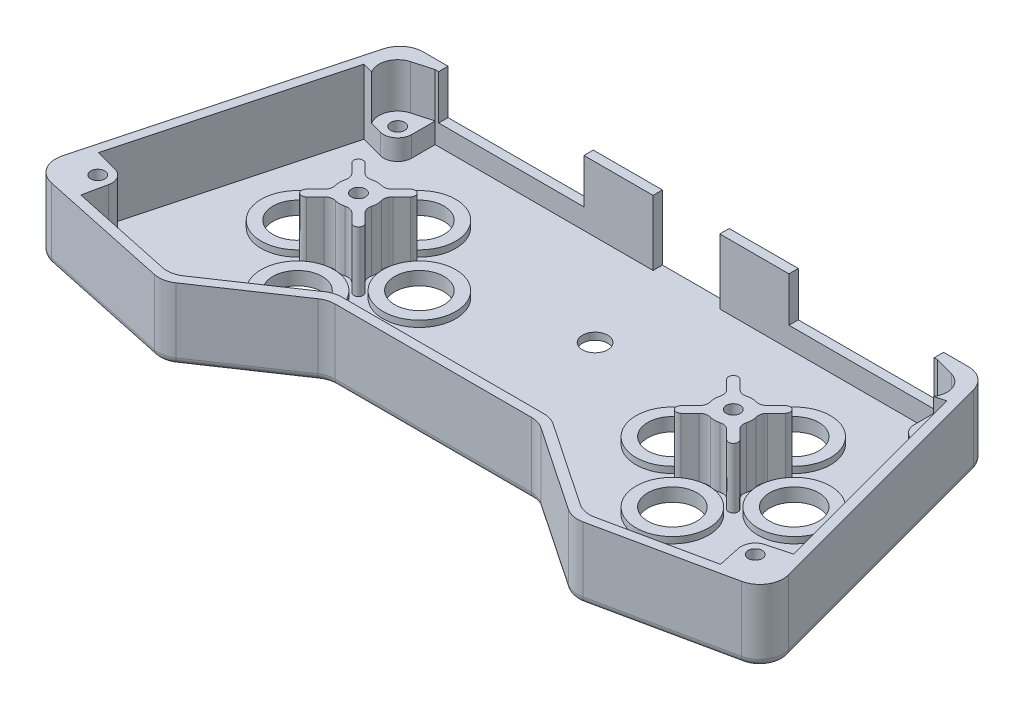
SolidWorks part; units mm, degrees
ref_plane "Front Plane" through (0, 0, 0) normal (0, 0, 1) x (1, 0, 0)
ref_plane "Top Plane" through (0, 0, 0) normal (0, 1, 0) x (1, 0, 0)
ref_plane "Right Plane" through (0, 0, 0) normal (1, 0, 0) x (0, 0, -1)
sketch "Sketch10" plane through (0, 0, 0) normal (0, 1, 0) x (1, 0, 0)
  line L0 (62, 32) -> (-62, 32)
  line L1 (-62, 32) -> (-78.8232, -30.7852)
  line L2 (-78.8232, -30.7852) -> (-43.6451, -38.2625)
  line L3 (-43.6451, -38.2625) -> (-22.5, -24)
  line L4 (-22.5, -24) -> (22.5, -24)
  line L5 (22.5, -24) -> (43.6451, -38.2625)
  line L6 (43.6451, -38.2625) -> (78.8232, -30.7852)
  line L7 (78.8232, -30.7852) -> (62, 32)
  line L8 (40, 13) -> (40, -13) construction
  line L9 (27, 0) -> (53, 0) construction
  line L10 (-40, 13) -> (-40, -13) construction
  line L11 (-53, 0) -> (-27, 0) construction
  line L12 (-27, 0) -> (27, 0) construction
  line L13 (0, 0) -> (0, 32) construction
  line L14 (0, 0) -> (0, -24) construction
  line L15 (78.8232, -30.7852) -> (22.5, -24) construction
  line L16 (-22.5, -24) -> (-78.8232, -30.7852) construction
  circle A0 centre (40, 13) radius 5.25
  circle A1 centre (27, 0) radius 5.25
  circle A2 centre (40, -13) radius 5.25
  circle A3 centre (53, 0) radius 5.25
  circle A4 centre (-40, 13) radius 5.25
  circle A5 centre (-53, 0) radius 5.25
  circle A6 centre (-40, -13) radius 5.25
  circle A7 centre (-27, 0) radius 5.25
  point P16 (40, 0)
  point P17 (-40, 0)
  dimension "D1" = 10.5
  dimension "D2" = 26
  dimension "D3" = 65
  dimension "D4" = 124
  dimension "D5" = 80
  dimension "D6" = 105
  dimension "D7" = 56
  dimension "D8" = 45
  dimension "D9" = 32
  dimension "D10" = 12
  dimension "D11" = 34
extrude "Boss-Extrude5" add sketch "Sketch10" along normal blind 1.5 separate body
sketch "Sketch11" plane through (0, 1.5, 0) normal (0, 1, 0) x (1, 0, 0)
  line L0 (-78.8232, -30.7852) -> (-62, 32)
  line L1 (-62, 32) -> (62, 32)
  line L2 (62, 32) -> (78.8232, -30.7852)
  line L3 (78.8232, -30.7852) -> (43.6451, -38.2625)
  line L4 (43.6451, -38.2625) -> (22.5, -24)
  line L5 (22.5, -24) -> (-22.5, -24)
  line L6 (-22.5, -24) -> (-43.6451, -38.2625)
  line L7 (-43.6451, -38.2625) -> (-78.8232, -30.7852)
  line L8 (-44.0596, -36.1297) -> (-76.3459, -29.2671)
  line L9 (-76.3459, -29.2671) -> (-60.4653, 30)
  line L10 (-60.4653, 30) -> (60.4653, 30)
  line L11 (60.4653, 30) -> (76.3459, -29.2671)
  line L12 (76.3459, -29.2671) -> (44.0596, -36.1297)
  line L13 (44.0596, -36.1297) -> (23.1115, -22)
  line L14 (23.1115, -22) -> (-23.1115, -22)
  line L15 (-23.1115, -22) -> (-44.0596, -36.1297)
  dimension "D1" = 2
extrude "Boss-Extrude7" add sketch "Sketch11" along direction (0, -1, 0) on the side of the normal offset from surface (13.875 mm away) 15.375 up to face at (-40, 0, 18.25)
fillet "Fillet4" radius 5 16 edges at (62, 7.6875, -32) (78.8232, 7.6875, 30.7852) (43.6451, 7.6875, 38.2625) (22.5, 7.6875, 24) (-22.5, 7.6875, 24) (-43.6451, 7.6875, 38.2625) (-62, 7.6875, -32) (-78.8232, 7.6875, 30.7852) (76.3459, 8.4375, 29.2671) (60.4653, 8.4375, -30) (44.0596, 8.4375, 36.1297) (23.1115, 8.4375, 22) (-23.1115, 8.4375, 22) (-44.0596, 8.4375, 36.1297) (-76.3459, 8.4375, 29.2671) (-60.4653, 8.4375, -30)
fillet "Fillet5" radius 1.5 16 edges at (43.7275, 0, 37.8387) (32.8264, 0, 30.9653) (22.4332, 0, 24.2185) (0, 0, 24) (-22.4332, 0, 24.2185) (-32.8264, 0, 30.9653) (-43.7275, 0, 37.8387) (-59.6953, 0, 34.851) (-76.8931, 0, 29.6024) (-70.2263, 0, -1.2991) (-61.2072, 0, -30.9668) (0, 0, -32) (61.2072, 0, -30.9668) (70.2263, 0, -1.2991) (76.8931, 0, 29.6024) (59.6953, 0, 34.851)
sketch "Sketch12" plane through (0, 1.5, 0) normal (0, 1, 0) x (1, 0, 0)
  line L0 (-62.2348, 23.3963) -> (-57.4052, 22.1022)
  line L1 (-61.4583, 26.2941) -> (-74.9822, -24.1777) construction
  line L2 (-53.6287, 25) -> (-53.6287, 30)
  line L3 (56.6287, 30) -> (-56.6287, 30) construction
  line L4 (-53.6287, 30) -> (-56.6287, 30)
  line L5 (-61.4583, 26.2941) -> (-62.2348, 23.3963)
  line L6 (-74.9822, -24.1777) -> (-74.2058, -21.2799)
  line L7 (-74.2058, -21.2799) -> (-69.3761, -22.574)
  line L8 (-67.2181, -26.0955) -> (-68.2577, -30.9863)
  line L9 (-71.1921, -30.3625) -> (-46.1356, -35.6885) construction
  line L10 (-68.2577, -30.9863) -> (-71.1921, -30.3625)
  line L11 (0, 0) -> (0, 17.9434) construction
  line L12 (68.2577, -30.9863) -> (71.1921, -30.3625)
  line L13 (67.2181, -26.0955) -> (68.2577, -30.9863)
  line L14 (74.2058, -21.2799) -> (69.3761, -22.574)
  line L15 (74.9822, -24.1777) -> (74.2058, -21.2799)
  line L16 (61.4583, 26.2941) -> (62.2348, 23.3963)
  line L17 (53.6287, 30) -> (56.6287, 30)
  line L18 (53.6287, 25) -> (53.6287, 30)
  line L19 (62.2348, 23.3963) -> (57.4052, 22.1022)
  arc A0 (-57.4052, 22.1022) -> (-53.6287, 25) centre (-56.6287, 25) ccw
  arc A1 (-56.6287, 30) -> (-61.4583, 26.2941) centre (-56.6287, 25) ccw
  arc A2 (-69.3761, -22.574) -> (-67.2181, -26.0955) centre (-70.1526, -25.4718) cw
  arc A3 (-71.1921, -30.3625) -> (-74.9822, -24.1777) centre (-70.1526, -25.4718) cw
  circle A4 centre (-56.6287, 25) radius 1.5
  circle A5 centre (-70.1526, -25.4718) radius 1.5
  circle A6 centre (70.1526, -25.4718) radius 1.5
  circle A7 centre (56.6287, 25) radius 1.5
  arc A8 (71.1921, -30.3625) -> (74.9822, -24.1777) centre (70.1526, -25.4718) ccw
  arc A9 (69.3761, -22.574) -> (67.2181, -26.0955) centre (70.1526, -25.4718) ccw
  arc A10 (56.6287, 30) -> (61.4583, 26.2941) centre (56.6287, 25) cw
  arc A11 (57.4052, 22.1022) -> (53.6287, 25) centre (56.6287, 25) cw
  dimension "D1" = 3
  dimension "D2" = 1.5
extrude "Boss-Extrude8" add sketch "Sketch12" along normal up to surface (13.875 mm away) up to face at (0, 15.375, 14.2385)
sketch "Sketch14" plane through (0, 0, -30) normal (0, 0, 1) x (1, 0, 0)
  line L0 (-53.6287, 15.375) -> (53.6287, 15.375) construction
  line L1 (-52.8787, 15.375) -> (-21.8787, 15.375)
  line L2 (-52.8787, 15.375) -> (-52.8787, 5.875)
  line L3 (-52.8787, 5.875) -> (-21.8787, 5.875)
  line L4 (-21.8787, 15.375) -> (-21.8787, 5.875)
  line L5 (0, 0) -> (0, 15.375) construction
  line L6 (21.8787, 15.375) -> (21.8787, 5.875)
  line L7 (52.8787, 5.875) -> (21.8787, 5.875)
  line L8 (52.8787, 15.375) -> (52.8787, 5.875)
  line L9 (52.8787, 15.375) -> (21.8787, 15.375)
  line L10 (-6.625, 14.53) -> (-6.625, 2) construction
  line L11 (-7.125, 15.375) -> (7.125, 15.375)
  line L12 (-7.125, 15.375) -> (-7.125, 1.5)
  line L13 (-7.125, 1.5) -> (7.125, 1.5)
  line L14 (7.125, 15.375) -> (7.125, 1.5)
  line L15 (53.6287, 1.5) -> (-53.6287, 1.5) construction
  dimension "D1" = 0.5
  dimension "D2" = 9.5
  dimension "D3" = 0.75
  dimension "D4" = 31
extrude "Cut-Extrude2" cut sketch "Sketch14" against normal through all
sketch "Sketch13" plane through (0, 15.375, 0) normal (0, 1, 0) x (1, 0, 0)
  line L0 (-57.7126, 28.8503) -> (-53.6287, 30)
  line L1 (-53.6287, 30) -> (-52.7213, 25.8555)
  line L2 (57.7126, 28.8503) -> (53.6287, 30)
  line L3 (53.6287, 30) -> (52.7213, 25.8555)
  arc A0 (-57.7126, 28.8503) -> (-52.7213, 25.8555) centre (-56.6287, 25) ccw
  arc A1 (52.7213, 25.8555) -> (57.7126, 28.8503) centre (56.6287, 25) ccw
  dimension "D1" = 8
extrude "Cut-Extrude1" cut sketch "Sketch13" against normal up to surface (9.5 mm away) up to face at (-37.3787, 5.875, -31)
sketch "Sketch15" plane through (0, 0, 0) normal (0, -1, 0) x (1, 0, 0)
  line L0 (0, -10.5) -> (0, -30.5) construction
  line L1 (-58.1634, -30.5) -> (58.1634, -30.5) construction
  circle A0 centre (0, -10.5) radius 2.7
  dimension "D2" = 5.4
  dimension "D1" = 20
extrude "Cut-Extrude3" cut sketch "Sketch15" against normal through all contours A0
sketch "Sketch16" plane through (0, 1.5, 0) normal (0, 1, 0) x (1, 0, 0)
  circle A0 centre (-40, 13) radius 7.75
  circle A1 centre (-40, 13) radius 5.25
  circle A2 centre (-27, 0) radius 7.75
  circle A3 centre (-27, 0) radius 5.25
  circle A4 centre (-53, 0) radius 5.25
  circle A5 centre (-53, 0) radius 7.75
  circle A6 centre (-40, -13) radius 5.25
  circle A7 centre (-40, -13) radius 7.75
  circle A8 centre (-40, 13) radius 5.25 construction
  circle A9 centre (-53, 0) radius 5.25 construction
  circle A10 centre (-40, -13) radius 5.25 construction
  circle A11 centre (-27, 0) radius 5.25 construction
  dimension "D1" = 2.5
extrude "Boss-Extrude9" add sketch "Sketch16" along normal blind 1.35
sketch "Sketch17" plane through (0, 1.5, 0) normal (0, 1, 0) x (1, 0, 0)
  line L0 (-43.4457, 2.0315) -> (-46.2741, 4.8599)
  line L3 (-44.8599, 6.2741) -> (-42.0315, 3.4457)
  line L4 (-37.9685, 3.4457) -> (-35.1401, 6.2741)
  line L5 (-33.7259, 4.8599) -> (-36.5543, 2.0315)
  line L6 (-36.5543, -2.0315) -> (-33.7259, -4.8599)
  line L7 (-35.1401, -6.2741) -> (-37.9685, -3.4457)
  line L8 (-42.0315, -3.4457) -> (-44.8599, -6.2741)
  line L9 (-46.2741, -4.8599) -> (-43.4457, -2.0315)
  line L10 (-45.567, -5.567) -> (-40, 0) construction
  line L11 (-40, 0) -> (-34.433, 5.567) construction
  line L12 (-34.433, -5.567) -> (-40, 0) construction
  line L13 (-45.567, 5.567) -> (-40, 0) construction
  line L14 (-45.567, 5.567) -> (-34.433, 5.567) construction
  line L15 (-40, 0) -> (0, 0) construction
  arc A0 (-43.4457, 2.0315) -> (-43.4457, -2.0315) centre (-40, 0) ccw
  arc A3 (-46.2741, 4.8599) -> (-44.8599, 6.2741) centre (-45.567, 5.567) cw
  arc A4 (-35.1401, 6.2741) -> (-33.7259, 4.8599) centre (-34.433, 5.567) cw
  arc A5 (-33.7259, -4.8599) -> (-35.1401, -6.2741) centre (-34.433, -5.567) cw
  arc A6 (-44.8599, -6.2741) -> (-46.2741, -4.8599) centre (-45.567, -5.567) cw
  arc A7 (-37.9685, 3.4457) -> (-42.0315, 3.4457) centre (-40, 0) ccw
  arc A8 (-36.5543, -2.0315) -> (-36.5543, 2.0315) centre (-40, 0) ccw
  arc A9 (-42.0315, -3.4457) -> (-37.9685, -3.4457) centre (-40, 0) ccw
  circle A10 centre (-40, 0) radius 1.5
  dimension "D1" = 40
  dimension "D4" = 8
  dimension "D5" = 3
  dimension "D2" = 2
  dimension "D3" = 4
extrude "Boss-Extrude10" add sketch "Sketch17" along normal offset from surface (12.875 mm away) 1 up to face at (-14.5019, 15.375, -31)
fillet "Fillet6" radius 2 8 edges at (-43.4457, 7.9375, 2.0315) (-43.4457, 7.9375, -2.0315) (-42.0315, 7.9375, -3.4457) (-37.9685, 7.9375, -3.4457) (-36.5543, 7.9375, -2.0315) (-36.5543, 7.9375, 2.0315) (-37.9685, 7.9375, 3.4457) (-42.0315, 7.9375, 3.4457)
mirror "Mirror1" about plane through (0, 0, 0) normal (1, 0, 0) of "Fillet6", "Boss-Extrude9", "Boss-Extrude10"
